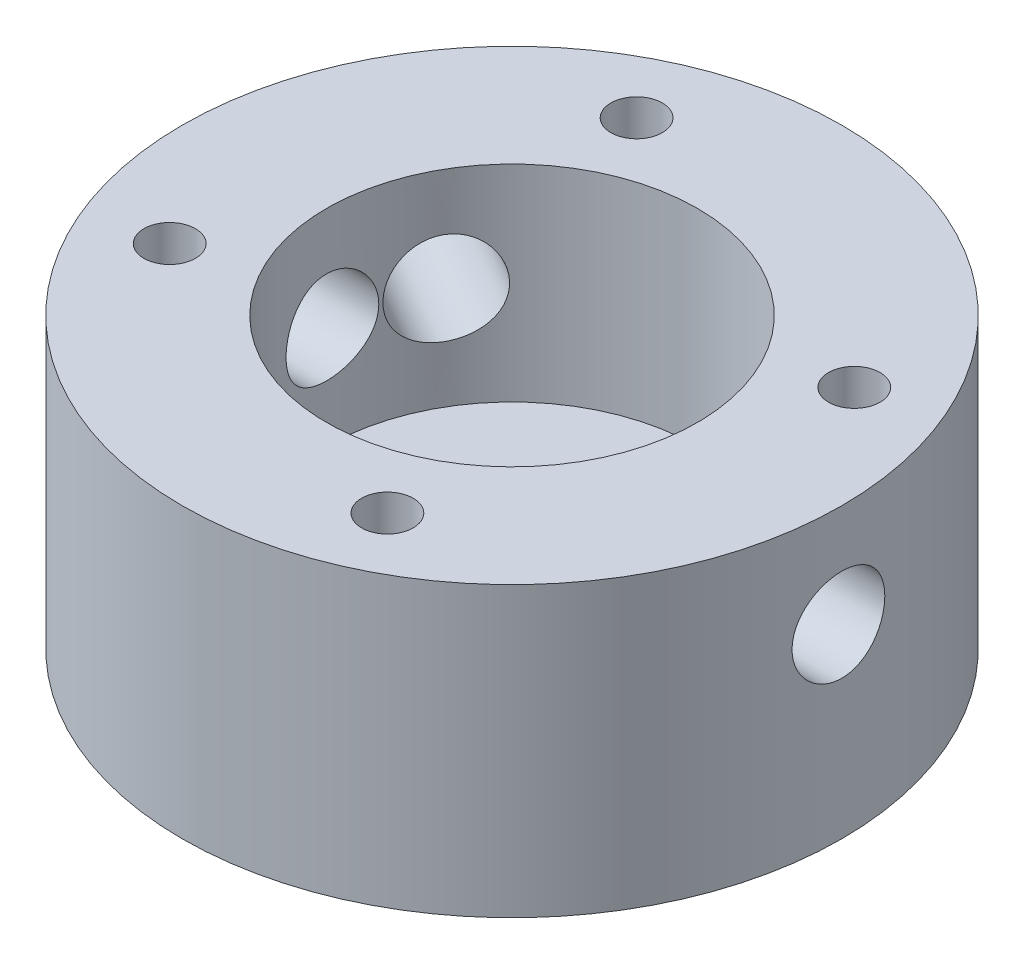
SolidWorks part; units mm, degrees
material "Chrome Stainless Steel"
ref_plane "Plano frontal" through (0, 0, 0) normal (0, 0, 1) x (1, 0, 0)
ref_plane "Plano superior" through (0, 0, 0) normal (0, 1, 0) x (1, 0, 0)
ref_plane "Plano direito" through (0, 0, 0) normal (1, 0, 0) x (0, 0, -1)
sketch "Esboço1" plane through (0, 0, 0) normal (0, 0, 1) x (1, 0, 0)
  line L0 (0, -9) -> (0, 0) construction
  line L1 (0, 0) -> (9, 0) construction
  line L2 (3, -9) -> (16, -9)
  line L3 (16, 5) -> (16, -9)
  line L4 (16, 5) -> (9, 5)
  line L5 (9, 5) -> (9, -5)
  line L6 (9, -5) -> (3, -5)
  line L7 (3, -5) -> (3, -9)
  line L8 (3, -9) -> (0, -9) construction
  dimension "D1" = 4
  dimension "D2" = 18
  dimension "D3" = 6
  dimension "D4" = 14
  dimension "D5" = 32
revolve "Revolução1" add sketch "Esboço1" angle 360 about L0
hole_wizard "Ø4.5 (4.5) Diameter Hole1" positions "3DSketch2" profile "Esboço4" hole size "Ø4.5" standard "ANSI Metric" end condition through all
sketch3d "3DSketch2"
  point P0 (0, 0, 0)
  point P4 (0, 0, 0)
  point P6 (16, 0, 0)
sketch "Esboço4" plane through (16, 0, 0) normal (0, 1, 0) x (0, 0, -1)
  line L0 (0, 0) -> (0, 32)
  line L1 (0, 32) -> (2.25, 32)
  line L2 (2.25, 32) -> (2.25, 0)
  line L5 (2.25, 0) -> (0, 0)
  line L11 (0, -6.35) -> (0, 107.95) construction
  dimension "Thru Hole Dia." = 4.5
  dimension "Thru Hole Depth" = 32
ref_plane "Plano1" through (-13.8564, 0, -8) normal (-0.866, 0, -0.5) x (0, -1, 0)
hole_wizard "Ø4.5 (4.5) Diameter Hole2" positions "Esboço6" profile "Esboço5" hole size "Ø4.5" standard "ANSI Metric"
sketch "Esboço6" plane through (-13.8564, 0, -8) normal (-0.866, 0, -0.5) x (0, -1, 0)
  point P0 (0, 0)
sketch "Esboço5" plane through (-13.8564, 0, -8) normal (0, 1, 0) x (-0.5, 0, 0.866)
  line L0 (0, 0) -> (0, 19.3519)
  line L1 (0, 19.3519) -> (2.25, 18)
  line L2 (2.25, 18) -> (2.25, 0)
  line L5 (2.25, 0) -> (0, 0)
  line L10 (0, 19.3519) -> (-2.25, 18) construction
  line L11 (0, -6.35) -> (0, 107.95) construction
  dimension "Hole Dia." = 4.5
  dimension "Hole Depth" = 18
  dimension "Drill Angle" = 118
ref_plane "Plano2" through (-16, 0, 0) normal (-1, 0, 0) x (0, -1, 0)
sketch "Esboço7" plane through (-16, 0, 0) normal (-1, 0, 0) x (0, -1, 0)
  circle A0 centre (0, 0) radius 3
  dimension "D1" = 6
extrude "Corte-extrusão1" [suppressed] cut sketch "Esboço7" against normal blind 6
ref_axis "Eixo1" through (0, 12.3, 0) along (0, -1, 0)
pattern_circular "PadrãoCircular1" [suppressed] count 2 every 17 about axis through (0, 12.3, 0) along (0, -1, 0) of bodies 131
pattern_circular "PadrãoCircular2" [suppressed] count 2 over 360 about axis through (0, 12.3, 0) along (0, -1, 0) of bodies 132
sketch "Esboço8" [suppressed] plane through (-16, 0, 0) normal (-1, 0, 0) x (0, -1, 0)
  line L0 (9.5, -16) -> (9.5, 16) construction
  line L1 (-6, -4) -> (9.5, -4)
  line L2 (-6, -4) -> (-6, 4)
  line L3 (-6, 4) -> (9.5, 4)
  line L4 (9.5, -4) -> (9.5, 4)
  circle A1 centre (0, 0) radius 3 construction
  dimension "D2" = 4
  dimension "D3" = 4
  dimension "D1" = 6
extrude "Corte-extrusão2" [suppressed] cut sketch "Esboço8" against normal blind 2
pattern_circular "PadrãoCircular3" [suppressed] count 2 every 17 about axis through (0, 12.3, 0) along (0, -1, 0) of bodies 134
pattern_circular "PadrãoCircular4" [suppressed] count 2 over 360 about axis through (0, 12.3, 0) along (0, -1, 0) of bodies 135
ref_plane "Plano3" through (0, -9, 0) normal (0, -1, 0) x (-1, 0, 0)
sketch "Esboço9" [suppressed] plane through (0, -9.5, 0) normal (0, -1, 0) x (-1, 0, 0)
  line L0 (14, -7.746) -> (14, 2.0923)
  line L1 (14, 2.0923) -> (11.1236, 11.5007)
  line L2 (12.2188, 7.9184) -> (14, 2.0923) construction
  line L3 (14, -4) -> (14, 2.0923) construction
  line L6 (-14, -7.746) -> (-14, 7.746)
  line L8 (-14, 4) -> (-14, -4) construction
  arc A0 (14, -7.746) -> (11.1236, 11.5007) centre (0, 0) ccw
  arc A1 (-14, 7.746) -> (-14, -7.746) centre (0, 0) ccw
extrude "Corte-extrusão3" [suppressed] cut sketch "Esboço9" against normal through all
ref_plane "Plano4" through (0, 5, 0) normal (0, 1, 0) x (1, 0, 0)
sketch "Esboço10" plane through (0, 5, 0) normal (0, 1, 0) x (1, 0, 0)
  line L0 (0, 23.071) -> (0, -16.8701) construction
  line L1 (-30.814, 0) -> (46.3723, 0) construction
  line L2 (0, 0) -> (-5.2827, 11.3288) construction
  circle A0 centre (0, 0) radius 12.5 construction
  circle A1 centre (-5.2827, 11.3288) radius 2
  dimension "D1" = 25
  dimension "D4" = 4
  dimension "D2" = 25
hole_wizard "M3x0.5 Tapped Hole1" positions "Sketch2" profile "Sketch1" tap size "M3x0.5" standard "ANSI Metric"
sketch "Sketch2" plane through (0, 5, 0) normal (0, -1, 0) x (-1, 0, 0)
  point P0 (5.2827, 11.3288)
sketch "Sketch1" plane through (-5.2827, 5, -11.3288) normal (1, 0, 0) x (0, 0, 1)
  line L0 (0, 0) -> (0, 12.7511)
  line L1 (0, 12.7511) -> (1.25, 12)
  line L2 (1.25, 12) -> (1.25, 0)
  line L5 (1.25, 0) -> (0, 0)
  line L10 (0, 12.7511) -> (-1.25, 12) construction
  line L11 (0, -6.35) -> (0, 107.95) construction
  dimension "Tap Drill Dia." = 2.5
  dimension "Tap Drill Depth" = 12
  dimension "Drill Angle" = 118
pattern_circular "CirPattern1" count 4 over 360 of "M3x0.5 Tapped Hole1" reverse direction yes
